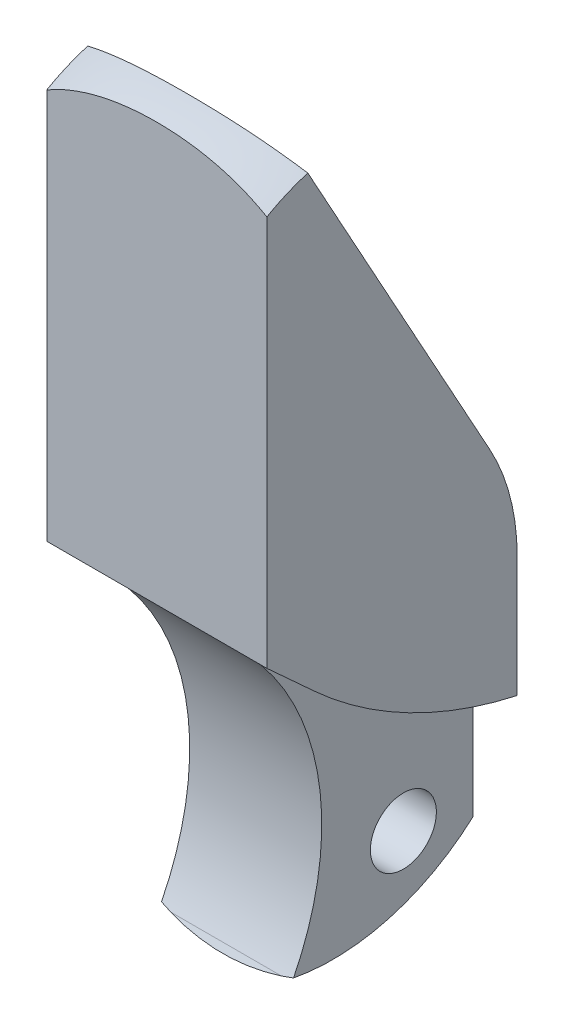
SolidWorks part; units mm, degrees
ref_plane "Front Plane" through (0, 0, 0) normal (0, 0, 1) x (1, 0, 0)
ref_plane "Top Plane" through (0, 0, 0) normal (0, 1, 0) x (1, 0, 0)
ref_plane "Right Plane" through (0, 0, 0) normal (1, 0, 0) x (0, 0, -1)
sketch "Sketch1" plane through (0, 0, 0) normal (0, 1, 0) x (1, 0, 0)
  circle A0 centre (0, 0) radius 10
extrude "Extrude1" add sketch "Sketch1" along normal blind 35
fillet "Fillet1" radius 10 1 edges at (0, 0, 10)
fillet "Скругление1" radius 8 1 edges at (0, 35, 10)
sketch "Sketch2" plane through (0, 0, 0) normal (0, 0, 1) x (1, 0, 0)
  line L0 (0, 40) -> (0, 29.5527) construction
  line L1 (3, 8.6646) -> (3, -4.7575)
  line L2 (-10.6723, 8.6646) -> (-3, 8.6646)
  line L3 (-10.6723, 8.6646) -> (-10.6723, -4.7575)
  line L4 (-10.6723, -4.7575) -> (-3, -4.7575)
  line L5 (-3, 8.6646) -> (-3, -4.7575)
  line L6 (10.6723, -4.7575) -> (3, -4.7575)
  line L7 (10.6723, 8.6646) -> (10.6723, -4.7575)
  line L8 (10.6723, 8.6646) -> (3, 8.6646)
  line L16 (10, 22.5) -> (24.8802, 22.5) construction
  dimension "D1" = 3
extrude "Extrude2" cut sketch "Sketch2" against normal mid plane 40
sketch "Sketch5" plane through (0, 0, 0) normal (0, 1, 0) x (1, 0, 0)
  line L0 (0, -10) -> (0, -4.7764) construction
  line L1 (11.4887, 10.9303) -> (5, 10.9303)
  line L2 (-11.4887, -10.0291) -> (-5, -10.0291)
  line L3 (-11.4887, -10.0291) -> (-11.4887, 10.9303)
  line L4 (-11.4887, 10.9303) -> (-5, 10.9303)
  line L5 (-5, -10.0291) -> (-5, 10.9303)
  line L6 (5, -10.0291) -> (5, 10.9303)
  line L7 (11.4887, -10.0291) -> (5, -10.0291)
  line L8 (11.4887, -10.0291) -> (11.4887, 10.9303)
  dimension "D1" = 5
extrude "Extrude4" cut sketch "Sketch5" along normal through all
sketch "Sketch7" plane through (0, 0, 0) normal (0, 1, 0) x (1, 0, 0)
  line L0 (0, 0) -> (11.986, 0) construction
  line L1 (-12.3124, -5) -> (12.0612, -5)
  line L2 (-12.3124, 12.9182) -> (12.0612, 12.9182)
  line L3 (-12.3124, 12.9182) -> (-12.3124, 6.375)
  line L4 (-12.3124, 6.375) -> (12.0612, 6.375)
  line L5 (12.0612, 12.9182) -> (12.0612, 6.375)
  line L6 (12.0612, -12.9182) -> (12.0612, -5)
  line L7 (-12.3124, -12.9182) -> (12.0612, -12.9182)
  line L8 (-12.3124, -12.9182) -> (-12.3124, -5)
  dimension "D1" = 5
extrude "Extrude6" cut sketch "Sketch7" against normal mid plane 92
sketch "Sketch10" plane through (3, 0, 0) normal (1, 0, 0) x (0, 0, -1)
  circle A0 centre (3.2028, 3.9183) radius 1.5
extrude "Cut-Extrude2" cut sketch "Sketch10" against normal through all
sketch "Sketch12" plane through (5, 0, 0) normal (1, 0, 0) x (0, 0, -1)
  line L0 (-5, 15.4219) -> (2.3805, 8.6646)
  line L1 (-5, 8.6646) -> (-5, 33.1874) construction
  line L2 (-5, 8.6646) -> (6.375, 8.6646) construction
  line L3 (2.3805, 8.6646) -> (-3.3753, -2.4329)
  line L4 (-3.3753, -2.4329) -> (-5, -2.4329)
  line L5 (-5, -2.4329) -> (-5, 15.4219)
extrude "Cut-Extrude3" cut sketch "Sketch12" against normal through all
fillet "Fillet2" radius 12 1 edges at (0, 8.6646, -2.3805)
fillet "Fillet3" radius 20 2 edges at (-4, 8.6646, -2.3805) (4, 8.6646, -2.3805)
sketch "Эскиз1" plane through (5, 0, 0) normal (1, 0, 0) x (0, 0, -1)
  line L0 (-4.197, 35.906) -> (7.7737, 35.906)
  line L1 (7.7737, 35.906) -> (7.7737, 14.1675)
  line L2 (7.7737, 14.1675) -> (-4.197, 35.906)
extrude "Вырез-Вытянуть1" cut sketch "Эскиз1" against normal through all
fillet "Скругление2" radius 10 1 edges at (0, 16.7075, -6.375)
